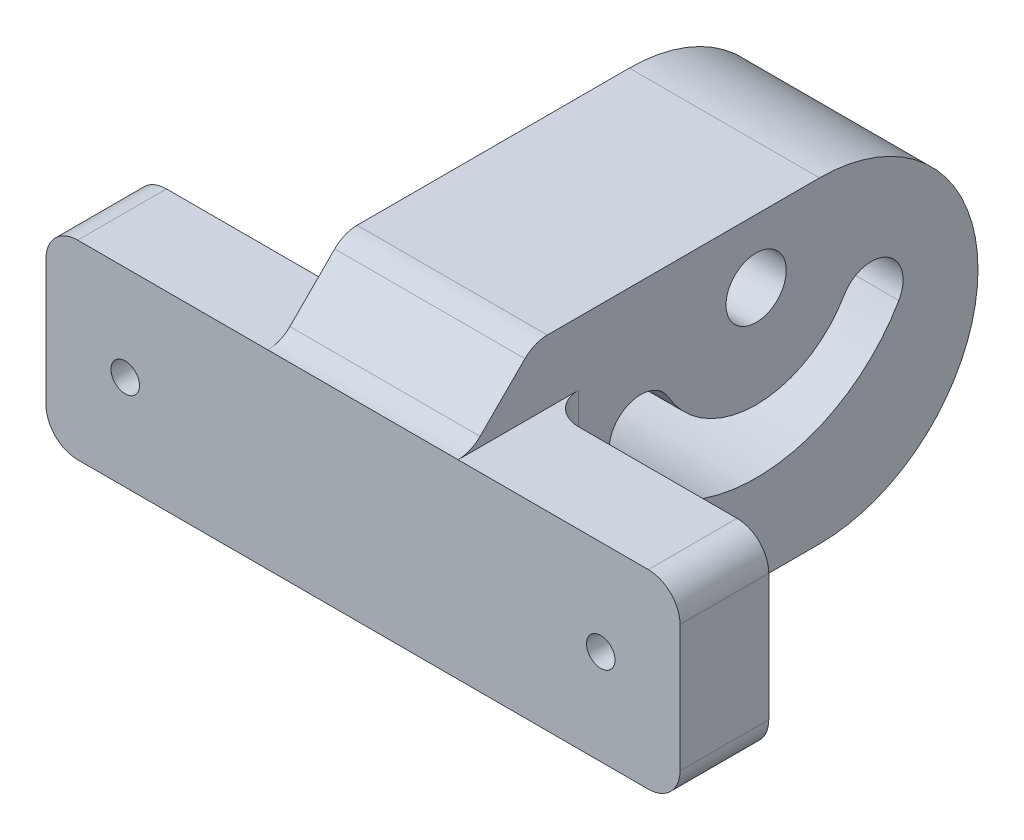
SolidWorks part; units mm, degrees
ref_plane "Front Plane" through (0, 0, 0) normal (0, 0, 1) x (1, 0, 0)
ref_plane "Top Plane" through (0, 0, 0) normal (0, 1, 0) x (1, 0, 0)
ref_plane "Right Plane" through (0, 0, 0) normal (1, 0, 0) x (0, 0, -1)
sketch "Sketch1" plane through (0, 0, -7) normal (0, 0, -1) x (-1, 0, 0)
  line L0 (0, 0) -> (0, -44) construction
  line L1 (-50, -14) -> (50, -14)
  line L2 (-50, -14) -> (-50, -44)
  line L3 (-50, -44) -> (50, -44)
  line L4 (50, -14) -> (50, -44)
  line L5 (-37.5, -29) -> (37.5, -29) construction
  dimension "D1" = 100
  dimension "D2" = 30
extrude "Boss-Extrude1" add sketch "Sketch1" along normal blind 14
sketch "Sketch2" plane through (0, 0, -21) normal (0, 0, -1) x (-1, 0, 0)
  line L0 (0, 0) -> (0, -44) construction
  line L1 (-50, -44) -> (50, -44) construction
  line L2 (-50, -29) -> (50, -29) construction
  line L3 (-50, -14) -> (-50, -44) construction
  line L4 (50, -44) -> (50, -14) construction
  circle A0 centre (-37.5, -29) radius 2.25
  circle A1 centre (37.5, -29) radius 2.25
  dimension "D2" = 4.5
  dimension "D1" = 75
extrude "Cut-Extrude1" cut sketch "Sketch2" against normal up to surface (14 mm away) up to face at (0, -29, -7)
sketch "Sketch3" plane through (0, 0, -21) normal (0, 0, -1) x (-1, 0, 0)
  circle A0 centre (-37.5, -29) radius 4.5
  circle A1 centre (37.5, -29) radius 4.5
  dimension "D1" = 9
extrude "Cut-Extrude2" cut sketch "Sketch3" against normal blind 4.4
sketch "Sketch5" plane through (0, 0, 0) normal (1, 0, 0) x (0, 0, -1)
  line L0 (9, -14) -> (19, -4)
  line L1 (21, -14) -> (7, -14) construction
  line L4 (19, -4) -> (89, -4)
  line L5 (89, -4) -> (89, -54)
  line L6 (21, -29) -> (105.9177, -29) construction
  line L7 (21, -14) -> (21, -44) construction
  line L8 (7, -105) -> (7, -13) construction
  line L9 (9, -14) -> (9, -44)
  line L10 (9, -44) -> (19, -54)
  line L11 (19, -54) -> (89, -54)
  point P18 (9, -29)
  point P19 (89, -29)
  dimension "D1" = 70
  dimension "D2" = 2
  dimension "D3" = 45
  dimension "D4" = 25
extrude "Boss-Extrude2" add sketch "Sketch5" along normal mid plane 30
sketch "Sketch6" plane through (0, 0, 0) normal (1, 0, 0) x (0, 0, -1)
  line L0 (89, -4) -> (19, -4) construction
  line L1 (89, -54) -> (89, -4) construction
  circle A0 centre (54, -14) radius 4.75
  dimension "D1" = 10
  dimension "D2" = 35
  dimension "D3" = 9.5
extrude "Cut-Extrude3" cut sketch "Sketch6" against normal through all both and the other way through all
fillet "Fillet1" radius 25 2 edges at (0, -4, -89) (0, -54, -89)
sketch "Sketch7" plane through (0, 0, 0) normal (1, 0, 0) x (0, 0, -1)
  line L0 (35.8135, -24.5) -> (54, -14) construction
  line L1 (54, -14) -> (54, -35) construction
  line L2 (54, -14) -> (72.1865, -24.5) construction
  circle A0 centre (54, -14) radius 21 construction
  arc A2 (35.8135, -24.5) -> (72.1865, -24.5) centre (54, -14) ccw construction
  arc A3 (31.4833, -27) -> (76.5167, -27) centre (54, -14) ccw
  arc A4 (40.1436, -22) -> (67.8564, -22) centre (54, -14) ccw
  arc A5 (40.1436, -22) -> (31.4833, -27) centre (35.8135, -24.5) ccw
  arc A6 (76.5167, -27) -> (67.8564, -22) centre (72.1865, -24.5) ccw
  point P5 (54, -35)
  dimension "D1" = 42
  dimension "D2" = 60
  dimension "D3" = 60
  dimension "D4" = 10
extrude "Cut-Extrude5" cut sketch "Sketch7" against normal through all both and the other way through all
fillet "Fillet2" radius 5 10 edges at (15, -29, -21) (0, -14, -9) (0, -44, -9) (-15, -29, -21) (50, -14, -14) (50, -44, -14) (-50, -44, -14) (-50, -14, -14) (0, -54, -19) (0, -4, -19)
